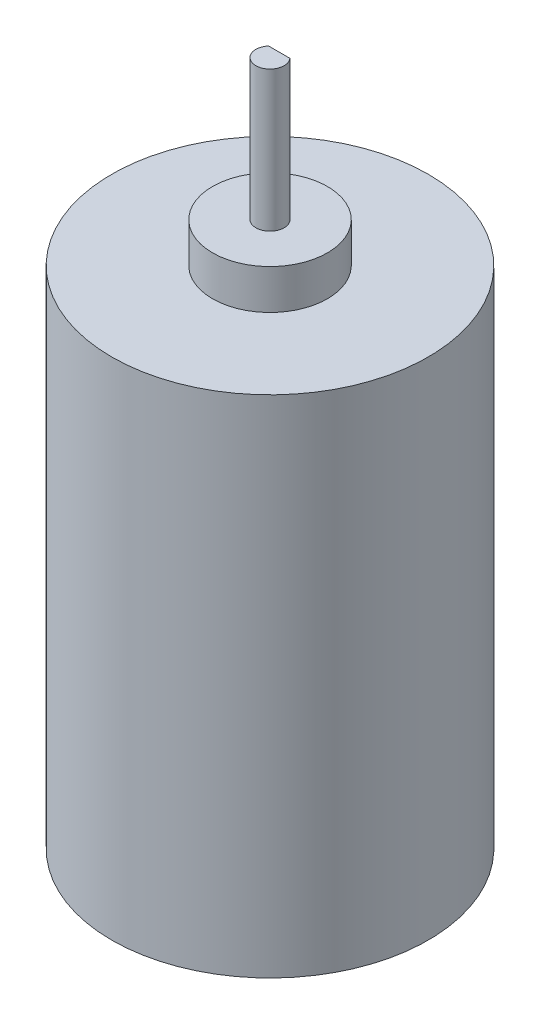
SolidWorks part; units mm, degrees
ref_plane "Front Plane" through (0, 0, 0) normal (0, 0, 1) x (1, 0, 0)
ref_plane "Top Plane" through (0, 0, 0) normal (0, 1, 0) x (1, 0, 0)
ref_plane "Right Plane" through (0, 0, 0) normal (1, 0, 0) x (0, 0, -1)
sketch "Sketch1" plane through (0, 0, 0) normal (0, 1, 0) x (1, 0, 0)
  line L0 (-1.2073, 1.05) -> (1.2073, 1.05)
  line L1 (0, 1.05) -> (0, -1.6)
  circle A0 centre (0, 0) radius 17.9
  circle A1 centre (0, 0) radius 6.5
  circle A2 centre (0, 0) radius 1.6
  dimension "D2" = 3.2
  dimension "D3" = 13
  dimension "D4" = 35.8
  dimension "D1" = 2.65
extrude "Boss-Extrude1" add sketch "Sketch1" against normal blind 57.12 contours A0 A1 | A1 A2 | A2 region at (-17.3937, 0, 0) region at (-6.3162, 0, 0)
extrude "Boss-Extrude2" add sketch "Sketch1<3>" along normal blind 4.5 contours A1 A2 | A2 region at (-6.3162, 0, 0)
sketch "Sketch1<3>" plane through (0, 0, 0) normal (0, 1, 0) x (1, 0, 0) same geometry as "Sketch1"
extrude "Boss-Extrude3" add sketch "Sketch1<4>" along normal blind 20.38 contours L1 A2 L0 | L0 A2 L1 region at (-0.7067, 0, 0.1647) region at (0.7067, 0, 0.1647)
sketch "Sketch1<4>" plane through (0, 0, 0) normal (0, 1, 0) x (1, 0, 0) same geometry as "Sketch1"
